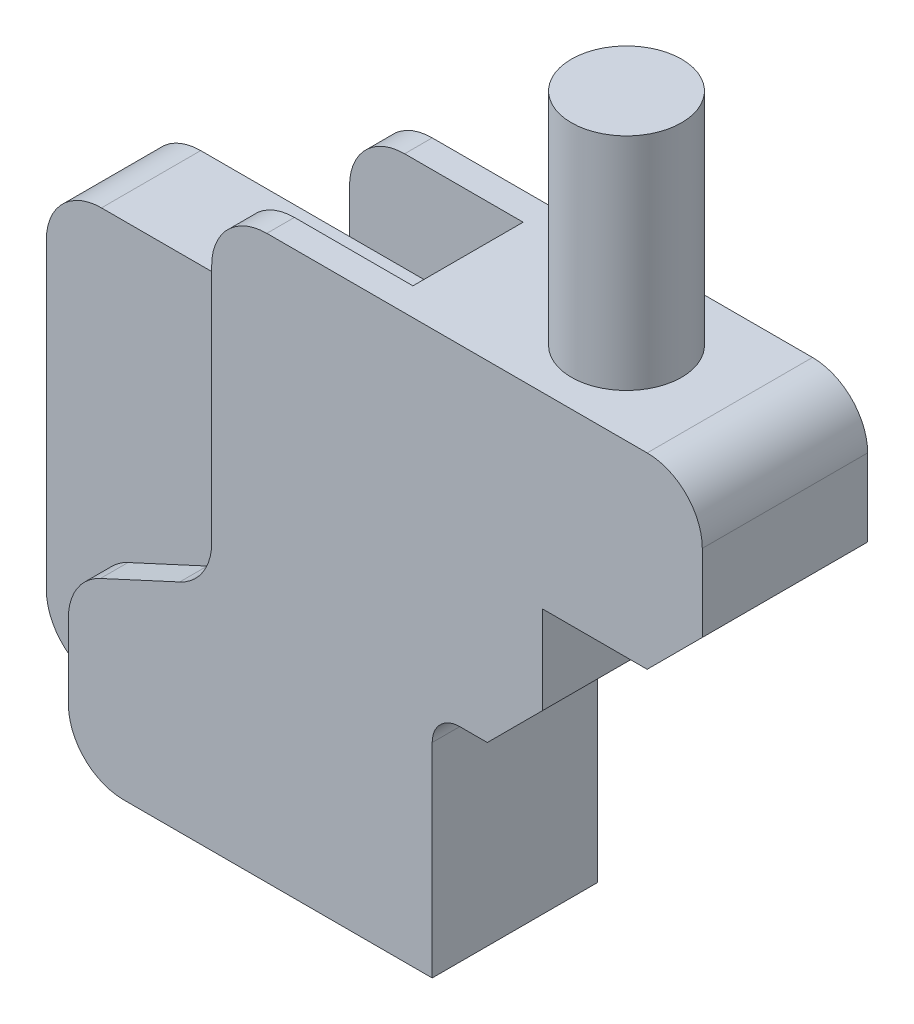
SolidWorks part; units mm, degrees
ref_plane "Front Plane" through (0, 0, 0) normal (0, 0, 1) x (1, 0, 0)
ref_plane "Top Plane" through (0, 0, 0) normal (0, 1, 0) x (1, 0, 0)
ref_plane "Right Plane" through (0, 0, 0) normal (1, 0, 0) x (0, 0, -1)
sketch "Sketch1" plane through (0, 0, 0) normal (0, 0, 1) x (1, 0, 0)
  line L0 (-51.6906, -18.3187) -> (-37.3094, -11.6813)
  line L1 (8.5, -51) -> (-47.5, -51)
  line L2 (57.5, 27) -> (57.5, 41)
  line L3 (47.5, 51) -> (-21.5, 51)
  line L4 (-57.5, -41) -> (-57.5, -27.3983)
  line L5 (57.5, -51) -> (-31.5, 27.9391) construction
  line L6 (57.5, 51) -> (-57.5, -51) construction
  line L7 (-31.5, -2.6017) -> (-31.5, 41)
  line L8 (8.5, -51) -> (8.5, -14)
  line L9 (13.5, -9) -> (18.5, -9)
  line L10 (28.5, 1) -> (28.5, 17)
  line L11 (28.5, 17) -> (47.5, 17)
  line L12 (47.5, 17) -> (57.5, 27)
  line L13 (18.5, -9) -> (28.5, 1)
  arc A0 (-47.5, -51) -> (-57.5, -41) centre (-47.5, -41) cw
  arc A1 (-57.5, -27.3983) -> (-51.6906, -18.3187) centre (-47.5, -27.3983) cw
  arc A2 (-37.3094, -11.6813) -> (-31.5, -2.6017) centre (-41.5, -2.6017) ccw
  arc A3 (57.5, 41) -> (47.5, 51) centre (47.5, 41) ccw
  arc A4 (-31.5, 41) -> (-21.5, 51) centre (-21.5, 41) cw
  arc A5 (8.5, -14) -> (13.5, -9) centre (13.5, -14) cw
  point P0 (0, 0)
  point P12 (28.5, -9)
  point P14 (57.5, 17)
  point P23 (-57.5, -21)
  point P26 (-31.5, -9)
  dimension "D2" = 10
  dimension "D10" = 5
  dimension "D1" = 115
  dimension "D3" = 34
  dimension "D4" = 60
  dimension "D5" = 29
  dimension "D6" = 49
  dimension "D7" = 40
  dimension "D8" = 60
  dimension "D9" = 30
extrude "Boss-Extrude1" add sketch "Sketch1" along normal blind 30
sketch "Sketch2" plane through (0, 51, 0) normal (0, 1, 0) x (1, 0, 0)
  line L0 (-57.5, -15) -> (57.5, -15) construction
  line L1 (-57.5, -30) -> (-57.5, 0) construction
  line L2 (57.5, -30) -> (57.5, 0) construction
  line L4 (-61.936, -5) -> (0, -5)
  line L5 (-61.936, -5) -> (-61.936, -25)
  line L6 (-61.936, -25) -> (0, -25)
  line L7 (0, -5) -> (0, -25)
  line L8 (-61.936, -5) -> (0, -25) construction
  line L9 (-61.936, -25) -> (0, -5) construction
  point P6 (-30.968, -15)
  dimension "D1" = 0
  dimension "D2" = 20
extrude "Cut-Extrude1" cut sketch "Sketch2" against normal blind 92
sketch "Sketch3" plane through (0, 51, 0) normal (0, 1, 0) x (1, 0, 0)
  line L0 (0, -15) -> (57.5, -15) construction
  line L1 (0, -25) -> (0, -5) construction
  line L2 (57.5, -30) -> (57.5, 0) construction
  circle A0 centre (28.75, -15) radius 10
  dimension "D1" = 20
extrude "Boss-Extrude2" add sketch "Sketch3" along normal blind 40
sketch "Sketch4" plane through (0, -41, 0) normal (0, 1, 0) x (1, 0, 0)
  line L0 (0, -15) -> (-67.5, -15) construction
  line L1 (0, -25) -> (0, -5) construction
  line L2 (0, -25) -> (0, -5) construction
  line L3 (-67.5, -6) -> (-1, -6)
  line L5 (-67.5, -24) -> (-1, -24)
  line L6 (-1, -6) -> (-1, -24)
  line L7 (-67.5, -9.8045) -> (-1, -24) construction
  line L8 (-67.5, -20.1955) -> (-1, -6) construction
  line L9 (-67.5, -6) -> (-67.5, -24)
  line L10 (0, -5) -> (-57.5, -5) construction
  line L11 (-57.5, -25) -> (0, -25) construction
  line L12 (-57.5, -25) -> (-57.5, -5) construction
  point P4 (-43.1613, -15)
  dimension "D1" = 1
  dimension "D2" = 1
  dimension "D3" = 1
  dimension "D4" = 10
extrude "Boss-Extrude3" add sketch "Sketch4" along normal blind 75
fillet "Fillet1" radius 10 1 edges at (-67.5, -41, 15)
fillet "Fillet2" radius 10 1 edges at (-67.5, 34, 15)
